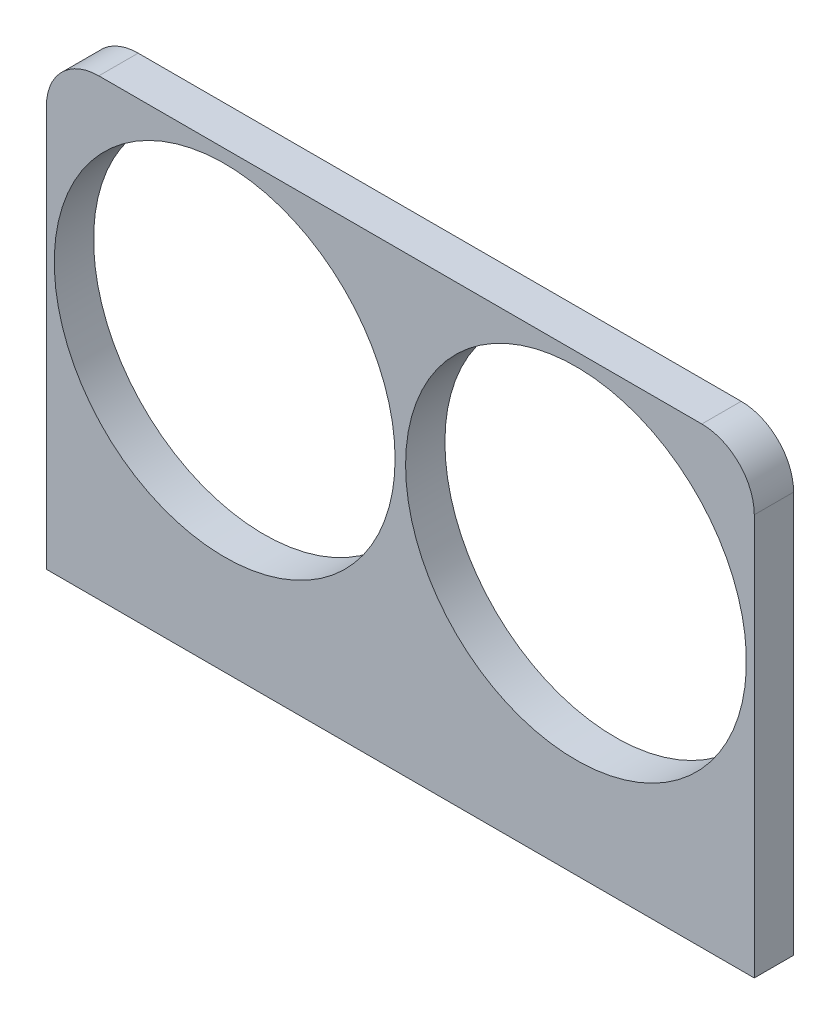
SolidWorks part; units mm, degrees
ref_plane "Front Plane" through (0, 0, 0) normal (0, 0, 1) x (1, 0, 0)
ref_plane "Top Plane" through (0, 0, 0) normal (0, 1, 0) x (1, 0, 0)
ref_plane "Right Plane" through (0, 0, 0) normal (1, 0, 0) x (0, 0, -1)
sketch "Sketch1" plane through (0, 0, 0) normal (0, 0, 1) x (1, 0, 0)
  line L0 (0, 8.65) -> (0, -5.1613) construction
  line L1 (-13.5, -8.65) -> (13.5, -8.65)
  line L2 (-13.5, -8.65) -> (-13.5, 8.65)
  line L3 (-13.5, 8.65) -> (13.5, 8.65)
  line L4 (13.5, -8.65) -> (13.5, 8.65)
  line L5 (-13.5, -8.65) -> (13.5, 8.65) construction
  line L6 (-13.5, 8.65) -> (13.5, -8.65) construction
  line L7 (-13.5, 1.65) -> (13.5, 1.65) construction
  circle A0 centre (-6.7, 1.65) radius 6.5
  circle A1 centre (6.7, 1.65) radius 6.5
  point P4 (0, 0)
  point P12 (9.3368, 15.6718)
  point P15 (0, 0)
  dimension "D1" = 13
  dimension "D2" = 6.8
  dimension "D3" = 7
  dimension "D4" = 27
  dimension "D5" = 17.3
extrude "Boss-Extrude1" add sketch "Sketch1" along normal blind 1.5
fillet "Fillet1" radius 2 2 edges at (13.5, 8.65, 0.75) (-13.5, 8.65, 0.75)
